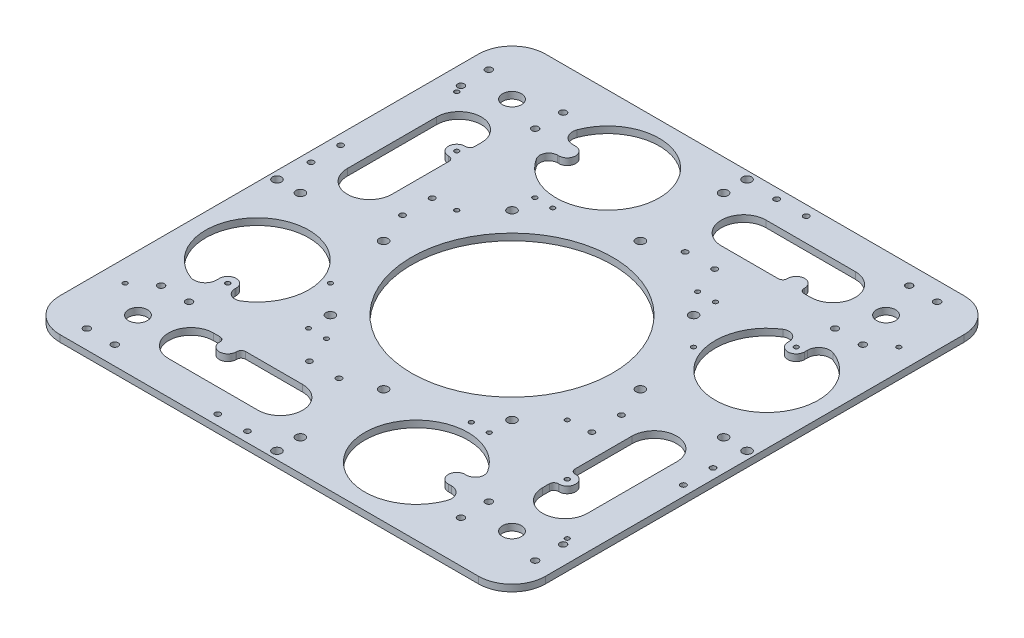
SolidWorks part; units mm, degrees
material "7075-T6 (SN)"
ref_plane "Front Plane" through (0, 0, 0) normal (0, 0, 1) x (1, 0, 0)
ref_plane "Top Plane" through (0, 0, 0) normal (0, 1, 0) x (1, 0, 0)
ref_plane "Right Plane" through (0, 0, 0) normal (1, 0, 0) x (0, 0, -1)
sketch "Sketch1" plane through (0, 0, 0) normal (0, 1, 0) x (1, 0, 0)
  line L0 (0, -189.5) -> (0, -210.5) construction
  line L1 (-167.5, -167.5) -> (167.5, -167.5) construction
  line L6 (-167.5, -167.5) -> (-167.5, 167.5) construction
  line L7 (-167.5, 167.5) -> (167.5, 167.5) construction
  line L9 (167.5, -167.5) -> (167.5, 167.5) construction
  line L10 (-167.5, -167.5) -> (167.5, 167.5) construction
  line L12 (-167.5, 167.5) -> (167.5, -167.5) construction
  line L15 (-217.5, -217.5) -> (217.5, -217.5)
  line L16 (-217.5, -217.5) -> (-217.5, 217.5)
  line L17 (-217.5, 217.5) -> (217.5, 217.5)
  line L18 (217.5, -217.5) -> (217.5, 217.5)
  line L19 (-217.5, -217.5) -> (217.5, 217.5) construction
  line L20 (-217.5, 217.5) -> (217.5, -217.5) construction
  circle A1 centre (0, 115) radius 4
  circle A2 centre (0, 0) radius 90
  circle A6 centre (0, 115) radius 12.5 construction
  circle A11 centre (-189.5, 0) radius 4
  circle A12 centre (-210.5, 0) radius 4
  circle A13 centre (0, -210.5) radius 4
  circle A14 centre (0, -189.5) radius 4
  circle A17 centre (81.3173, 81.3173) radius 4
  circle A18 centre (115, 0) radius 4
  circle A19 centre (81.3173, -81.3173) radius 4
  circle A20 centre (0, -115) radius 4
  circle A21 centre (-81.3173, -81.3173) radius 4
  circle A22 centre (-115, 0) radius 4
  circle A23 centre (-81.3173, 81.3173) radius 4
  circle A28 centre (0, 189.5) radius 4
  circle A29 centre (0, 210.5) radius 4
  circle A30 centre (189.5, 0) radius 4
  circle A31 centre (210.5, 0) radius 4
  circle A32 centre (167.5, 167.5) radius 8.5
  circle A33 centre (167.5, -167.5) radius 8.5
  circle A34 centre (-167.5, -167.5) radius 8.5
  circle A35 centre (-167.5, 167.5) radius 8.5
  point P5 (0, 0)
  point P6 (0, 0)
  point P12 (0, 0)
  point P73 (0, 0)
  dimension "D2" = 8
  dimension "D4" = 180
  dimension "D6" = 25
  dimension "D7" = 435
  dimension "D8" = 435
  dimension "D9" = 7
  dimension "D11" = 335
  dimension "D13" = 17
  dimension "D3" = 115
  dimension "D5" = 4
  dimension "D10" = 21
  dimension "D12" = 335
  dimension "D14" = 4
extrude "Boss-Extrude1" add sketch "Sketch1" along normal blind 6
sketch "Sketch2" plane through (0, 6, 0) normal (0, 1, 0) x (1, 0, 0)
  line L0 (-69, -194.3407) -> (-69, -140.6593) construction
  line L1 (0, -217.5) -> (0, -117.5) construction
  line L2 (-200, -217.5) -> (0, -217.5) construction
  line L3 (0, -117.5) -> (-200, -117.5) construction
  line L4 (-200, -117.5) -> (-200, -217.5) construction
  line L5 (-200, -167.5) -> (0, -167.5) construction
  line L10 (-200, -167.5) -> (-167.5, -167.5) construction
  line L11 (-55, -126.5) -> (-55, -208.5) construction
  line L12 (-55, -208.5) -> (-28.5, -208.5) construction
  line L13 (-28.5, -208.5) -> (-28.5, -126.5) construction
  line L14 (-28.5, -126.5) -> (-55, -126.5) construction
  line L15 (-155, -200.7433) -> (-180, -134.2567) construction
  line L16 (-155, -134.2567) -> (-180, -200.7433) construction
  circle A10 centre (-167.5, -167.5) radius 8.5 construction
  circle A13 centre (-167.5, -167.5) radius 8.5
  circle A15 centre (-28.5, -126.5) radius 2.5
  circle A16 centre (-55, -126.5) radius 2.5
  circle A17 centre (-55, -208.5) radius 2.5
  circle A18 centre (-28.5, -208.5) radius 2.5
  circle A19 centre (-167.5, -167.5) radius 9.5
  circle A20 centre (-180, -134.2567) radius 3
  circle A21 centre (-155, -134.2567) radius 3
  circle A22 centre (-155, -200.7433) radius 3
  circle A23 centre (-180, -200.7433) radius 3
  dimension "D1" = 19
  dimension "D2" = 112.5
  dimension "D3" = 26.5
  dimension "D4" = 82
  dimension "D5" = 32.5
  dimension "D6" = 14
extrude "Cut-Extrude1" cut sketch "Sketch2" against normal blind 10 contours A21 | A20 | A23 | A22 | A17 | A18 | A15 | A16
pattern_circular "CirPattern1" count 4 over 360 about axis through (0, 6, 0) along (0, -1, 0) of "Cut-Extrude1"
fillet "Fillet1" radius 30 4 edges at (217.5, 3, 217.5) (217.5, 3, -217.5) (-217.5, 3, 217.5) (-217.5, 3, -217.5)
sketch "Sketch4" plane through (0, 6, 0) normal (0, 1, 0) x (1, 0, 0)
  line L1 (-81.3173, 93.3173) -> (81.3173, 93.3173) construction
  line L4 (0, 0) -> (0, 93.3173) construction
  line L5 (0, 0) -> (115, 0) construction
  line L6 (87.9, 91.3173) -> (57.9, 91.3173) construction
  line L7 (-57.9, 91.3173) -> (-87.9, 91.3173) construction
  line L8 (72.85, 93.3173) -> (-72.85, 93.3173) construction
  line L9 (72.85, -93.3173) -> (-72.85, -93.3173) construction
  line L10 (-57.9, -91.3173) -> (-87.9, -91.3173) construction
  line L11 (87.9, -91.3173) -> (57.9, -91.3173) construction
  line L12 (-81.3173, -93.3173) -> (81.3173, -93.3173) construction
  circle A0 centre (-81.3173, 81.3173) radius 12 construction
  circle A1 centre (81.3173, 81.3173) radius 12 construction
  circle A6 centre (80.9, 101.3173) radius 2
  circle A7 centre (64.9, 101.3173) radius 2
  circle A8 centre (-80.9, 101.3173) radius 2
  circle A9 centre (-64.9, 101.3173) radius 2
  circle A10 centre (81.3173, -81.3173) radius 12 construction
  circle A11 centre (-81.3173, -81.3173) radius 12 construction
  circle A12 centre (-64.9, -101.3173) radius 2
  circle A13 centre (-80.9, -101.3173) radius 2
  circle A14 centre (64.9, -101.3173) radius 2
  circle A15 centre (80.9, -101.3173) radius 2
  dimension "D1" = 24
  dimension "D2" = 24
extrude "Cut-Extrude3" cut sketch "Sketch4" against normal blind 10
sketch "Sketch6" plane through (0, 6, 0) normal (0, 1, 0) x (1, 0, 0)
  line L0 (-167.5, -167.5) -> (-81.3173, -81.3173) construction
  line L1 (-81.3173, -81.3173) -> (-106.066, -56.5685) construction
  line L12 (-98.9949, -49.4975) -> (-205.061, -155.5635) construction
  line L13 (-152.028, -102.5305) -> (-127.2792, -127.2792) construction
  line L14 (-197.9899, -148.4924) -> (-173.2412, -173.2412) construction
  line L15 (-106.066, -56.5685) -> (-81.3173, -81.3173) construction
  line L16 (-81.3173, -81.3173) -> (-56.5685, -106.066) construction
  line L17 (-102.5305, -152.028) -> (-127.2792, -127.2792) construction
  line L18 (-148.4924, -197.9899) -> (-173.2412, -173.2412) construction
  line L19 (-49.4975, -98.9949) -> (-155.5635, -205.061) construction
  line L20 (-49.4975, 98.9949) -> (-155.5635, 205.061) construction
  line L21 (-148.4924, 197.9899) -> (-173.2412, 173.2412) construction
  line L22 (-102.5305, 152.028) -> (-127.2792, 127.2792) construction
  line L23 (-81.3173, 81.3173) -> (-56.5685, 106.066) construction
  line L24 (-167.5, 167.5) -> (-81.3173, 81.3173) construction
  line L25 (-152.028, 102.5305) -> (-127.2792, 127.2792) construction
  line L26 (-81.3173, 81.3173) -> (-106.066, 56.5685) construction
  line L27 (-98.9949, 49.4975) -> (-205.061, 155.5635) construction
  line L28 (-197.9899, 148.4924) -> (-173.2412, 173.2412) construction
  line L29 (98.9949, 49.4975) -> (205.061, 155.5635) construction
  line L30 (197.9899, 148.4924) -> (173.2412, 173.2412) construction
  line L31 (152.028, 102.5305) -> (127.2792, 127.2792) construction
  line L32 (81.3173, 81.3173) -> (106.066, 56.5685) construction
  line L33 (167.5, 167.5) -> (81.3173, 81.3173) construction
  line L34 (102.5305, 152.028) -> (127.2792, 127.2792) construction
  line L35 (81.3173, 81.3173) -> (56.5685, 106.066) construction
  line L36 (49.4975, 98.9949) -> (155.5635, 205.061) construction
  line L37 (148.4924, 197.9899) -> (173.2412, 173.2412) construction
  line L38 (49.4975, -98.9949) -> (155.5635, -205.061) construction
  line L39 (148.4924, -197.9899) -> (173.2412, -173.2412) construction
  line L40 (102.5305, -152.028) -> (127.2792, -127.2792) construction
  line L41 (81.3173, -81.3173) -> (56.5685, -106.066) construction
  line L42 (167.5, -167.5) -> (81.3173, -81.3173) construction
  line L43 (152.028, -102.5305) -> (127.2792, -127.2792) construction
  line L44 (81.3173, -81.3173) -> (106.066, -56.5685) construction
  line L45 (98.9949, -49.4975) -> (205.061, -155.5635) construction
  line L46 (197.9899, -148.4924) -> (173.2412, -173.2412) construction
  circle A3 centre (-152.028, -102.5305) radius 2
  circle A4 centre (-197.9899, -148.4924) radius 2
  circle A5 centre (-106.066, -56.5685) radius 2
  circle A6 centre (-56.5685, -106.066) radius 2 construction
  circle A7 centre (-102.5305, -152.028) radius 2 construction
  circle A8 centre (-148.4924, -197.9899) radius 2 construction
  circle A9 centre (0, 0) radius 90 construction
  circle A10 centre (0, 0) radius 90 construction
  circle A11 centre (-56.5685, 106.066) radius 2 construction
  circle A12 centre (-102.5305, 152.028) radius 2 construction
  circle A13 centre (-148.4924, 197.9899) radius 2 construction
  circle A14 centre (-197.9899, 148.4924) radius 2
  circle A15 centre (-152.028, 102.5305) radius 2
  circle A16 centre (-106.066, 56.5685) radius 2
  circle A17 centre (106.066, 56.5685) radius 2
  circle A18 centre (152.028, 102.5305) radius 2
  circle A19 centre (197.9899, 148.4924) radius 2
  circle A20 centre (148.4924, 197.9899) radius 2 construction
  circle A21 centre (102.5305, 152.028) radius 2 construction
  circle A22 centre (56.5685, 106.066) radius 2 construction
  circle A23 centre (56.5685, -106.066) radius 2 construction
  circle A24 centre (102.5305, -152.028) radius 2 construction
  circle A25 centre (148.4924, -197.9899) radius 2 construction
  circle A26 centre (197.9899, -148.4924) radius 2
  circle A27 centre (152.028, -102.5305) radius 2
  circle A28 centre (106.066, -56.5685) radius 2
  dimension "D3" = 10
  dimension "D4" = 4
  dimension "D5" = 65
  dimension "D6" = 65
  dimension "D1" = 35
  dimension "D2" = 140
  dimension "D7" = 4
extrude "Cut-Extrude4" cut sketch "Sketch6" against normal blind 10 contours A14 | A15 | A16 | A4 | A3 | A5 | A28 | A27 | A26 | A17 | A18 | A19
sketch "Sketch3" plane through (0, 6, 0) normal (0, 1, 0) x (1, 0, 0)
  line L0 (25, -156.8979) -> (25, -217.5) construction
  line L1 (0, -210.5) -> (25, -210.5) construction
  line L2 (-187.5, -217.5) -> (187.5, -217.5) construction
  line L3 (-120, -167.5) -> (-40, -167.5) construction
  line L6 (-120, -147.5) -> (-114.0305, -147.5)
  line L7 (-120, -187.5) -> (-40, -187.5)
  line L8 (-167.5, -167.5) -> (-30, -167.5) construction
  line L12 (134.2567, -180) -> (134.2567, -155) construction
  line L13 (117.4967, -217.5) -> (117.4967, -156.8979) construction
  line L14 (117.4967, -180) -> (117.4967, -155) construction
  line L15 (-187.5, -217.5) -> (187.5, -217.5) construction
  line L18 (-95.0305, -152.028) -> (-95.0305, -151.5)
  line L19 (-110.0305, -152.028) -> (-110.0305, -151.5)
  line L21 (-91.0305, -147.5) -> (-40, -147.5)
  line L46 (-102.5305, -152.028) -> (-102.5305, -147.5) construction
  line L48 (102.5305, -159.528) -> (105.2252, -159.528)
  line L49 (102.5305, -144.528) -> (103.6212, -144.528)
  circle A0 centre (0, -115) radius 30 construction
  circle A1 centre (81.3173, -81.3173) radius 30 construction
  arc A3 (-120, -147.5) -> (-120, -187.5) centre (-120, -167.5) ccw
  arc A4 (-40, -187.5) -> (-40, -147.5) centre (-40, -167.5) ccw
  arc A5 (110.3923, -132.2674) -> (114.5985, -173.0123) centre (71.2484, -156.8979) ccw
  arc A6 (-91.0305, -147.5) -> (-95.0305, -151.5) centre (-91.0305, -151.5) ccw
  arc A11 (-110.0305, -152.028) -> (-95.0305, -152.028) centre (-102.5305, -152.028) ccw
  arc A16 (-114.0305, -147.5) -> (-110.0305, -151.5) centre (-114.0305, -151.5) cw
  arc A37 (103.6212, -144.528) -> (110.3923, -132.2674) centre (103.6212, -136.528) ccw
  arc A38 (102.5305, -144.528) -> (102.5305, -159.528) centre (102.5305, -152.028) ccw
  arc A39 (105.2252, -159.528) -> (114.5985, -173.0123) centre (105.2252, -169.528) cw
  point P17 (-80, -167.5)
  dimension "D1" = 15
  dimension "D2" = 60
  dimension "D5" = 20
  dimension "D7" = 4
  dimension "D3" = 25
  dimension "D4" = 80
  dimension "D6" = 16.76
extrude "Cut-Extrude6" cut sketch "Sketch3" against normal blind 10 contours L21 L6 A3 L7 A4 | A39 L48 A38 L49 A37 A5 region at (-79.1439, 6, 168.064) region at (69.0357, 6, 157.1861)
pattern_circular "CirPattern3" count 4 over 360 about axis through (0, 6, 0) along (0, -1, 0) of "Cut-Extrude6" reverse direction yes
